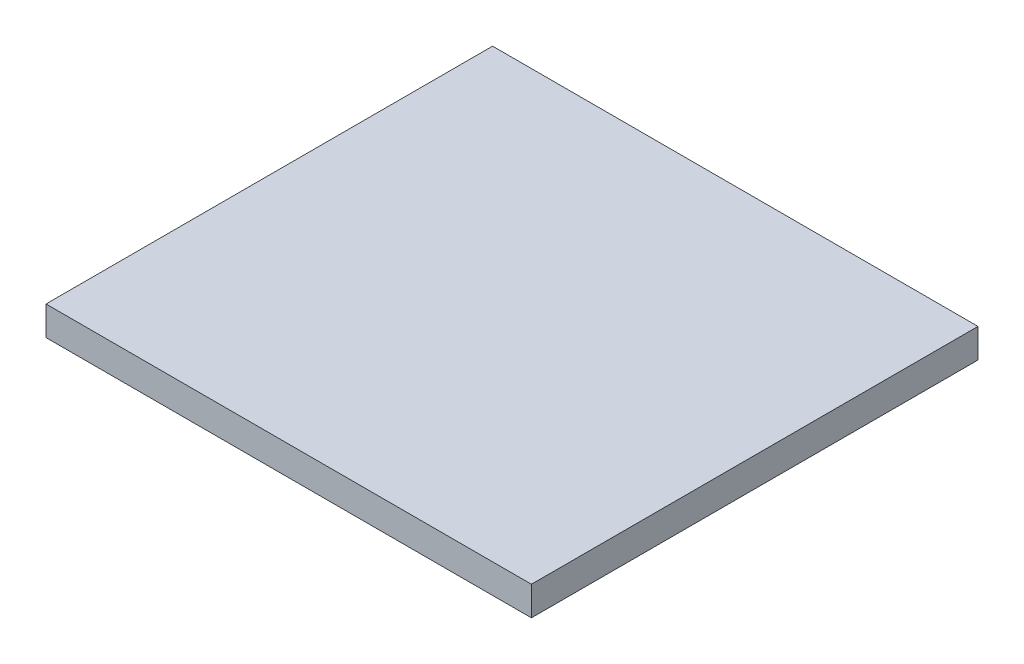
SolidWorks part; units mm, degrees
material "Maple"
ref_plane "Front Plane" through (0, 0, 0) normal (0, 0, 1) x (1, 0, 0)
ref_plane "Top Plane" through (0, 0, 0) normal (0, 1, 0) x (1, 0, 0)
ref_plane "Right Plane" through (0, 0, 0) normal (1, 0, 0) x (0, 0, -1)
sketch "Sketch1" plane through (0, 0, 0) normal (0, 1, 0) x (1, 0, 0)
  line L0 (140, 92) -> (0, 92) construction
  line L1 (0, 0) -> (100, 0)
  line L2 (0, 0) -> (0, 92)
  line L3 (0, 92) -> (100, 92)
  line L4 (100, 0) -> (100, 92)
  line L5 (100, 12) -> (100, 80) construction
extrude "Boss-Extrude1" add sketch "Sketch1" along normal blind 6
ref_plane "Plane1" through (0, 3, 0) normal (0, 1, 0) x (1, 0, 0)
